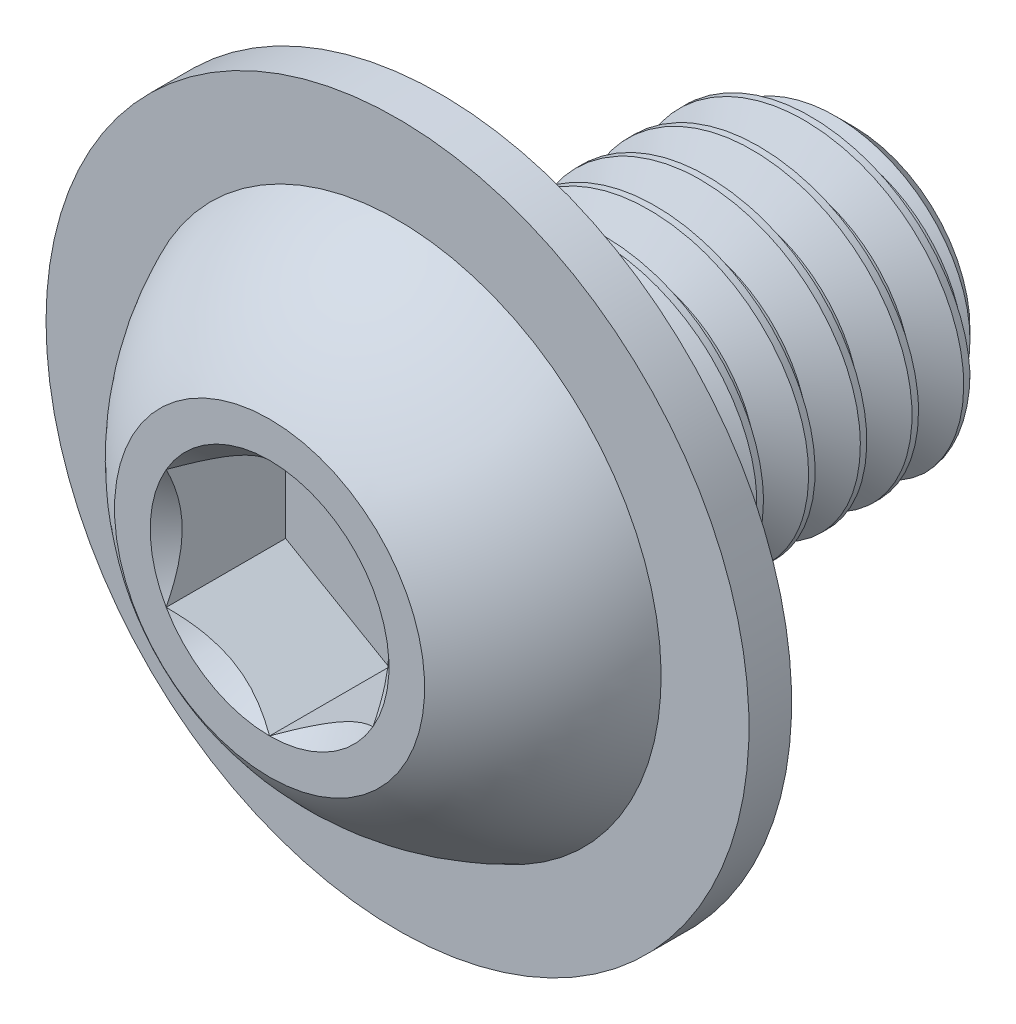
SolidWorks part; units mm, degrees
ref_plane "Front" through (0, 0, 0) normal (0, 0, 1) x (1, 0, 0)
ref_plane "Top" through (0, 0, 0) normal (0, 1, 0) x (1, 0, 0)
ref_plane "Right" through (0, 0, 0) normal (1, 0, 0) x (0, 0, -1)
sketch "Sketch1" plane through (0, 0, 0) normal (1, 0, 0) x (0, 0, -1)
  line L2 (3.3, 3) -> (11.3, 3)
  line L3 (11.3, 3) -> (11.3, 0)
  line L4 (11.3, 0) -> (3.3, 0)
  line L6 (2.475, 5.1) -> (3.3, 5.1) construction
  line L7 (11.3, 3) -> (11.3, -3) construction
  line L8 (0, 0) -> (3.3, 0) construction
  line L9 (3.3, 5.1) -> (3.3, -5.1) construction
  line L11 (3.3, 3) -> (3.3, 0)
  line L13 (0, 2) -> (0, -2) construction
  line L14 (0, 2) -> (0, 3) construction
  line L15 (2.475, 5.1) -> (2.475, 6.8) construction
  line L16 (2.475, 6.8) -> (3.3, 6.8) construction
  line L17 (3.3, 6.8) -> (3.3, 5.1) construction
  line L18 (3.3, 6.8) -> (3.3, -6.8) construction
  arc A3 (0, 3) -> (2.475, 5.1) centre (4.6739, 0) cw construction
  dimension "D1" = 0.825
revolve "Revolve1" add sketch "Sketch1" angle 360 mid plane about L4
sketch "Sketch3" plane through (0, 0, -11.3) normal (0, 0, -1) x (-1, 0, 0)
  circle A0 centre (0, 0) radius 3
curve "Helix/Spiral1" pitch 1 height 9 turns 9
sketch "Sketch2" plane through (0, 0, 0) normal (1, 0, 0) x (0, 0, -1)
  line L0 (11.3, 3) -> (12.175, 3)
  line L1 (12.175, 3) -> (11.8, 2.3505)
  line L2 (11.8, 2.3505) -> (11.675, 2.3505)
  line L3 (11.675, 2.3505) -> (11.3, 3)
  line L4 (11.4875, 2.6752) -> (11.9875, 2.6752) construction
  dimension "D1" = 60
  dimension "D2" = 0.125
  dimension "D3" = 0.5
chamfer "Chamfer1" distance 0.75 angle 45 1 edges at (0, 3, -11.3)
sweep "Cut-Sweep1" cut profiles "Sketch2" path "Helix/Spiral1" align with end faces yes
sketch "Sketch7" plane through (0, 0, 0) normal (1, 0, 0) x (0, 0, -1)
  line L6 (2.475, 5.1) -> (3.3, 5.1) construction
  line L8 (0, 0) -> (3.3, 0) construction
  line L11 (3.3, 5.1) -> (3.3, -5.1) construction
  line L12 (2.475, 5.1) -> (3.3, 5.1)
  line L13 (0, 0) -> (3.3, 0)
  line L14 (0, 2) -> (0, -2) construction
  line L15 (3.3, 5.1) -> (3.3, 0)
  line L16 (0, 3) -> (0, 0)
  arc A2 (2.475, 5.1) -> (0, 3) centre (4.6739, 0) ccw construction
  arc A3 (2.475, 5.1) -> (0, 3) centre (4.6739, 0) ccw
revolve "Revolve2" add sketch "Sketch7" angle 360 mid plane about L13
sketch "Sketch11" plane through (0, 0, -3.3) normal (0, 0, -1) x (-1, 0, 0)
  circle A0 centre (0, 0) radius 6.8
extrude "Boss-Extrude3" add sketch "Sketch11" against normal up to vertex (0.825 mm away) up to point (0, 5.1, -2.475)
sketch "Sketch5" plane through (0, 0, 0) normal (0, 0, 1) x (1, 0, 0)
  line L1 (2, -1.1547) -> (2, 1.1547)
  line L2 (2, 1.1547) -> (0, 2.3094)
  line L3 (0, 2.3094) -> (-2, 1.1547)
  line L4 (-2, 1.1547) -> (-2, -1.1547)
  line L5 (-2, -1.1547) -> (0, -2.3094)
  line L6 (0, -2.3094) -> (2, -1.1547)
  circle A0 centre (0, 0) radius 2 construction
extrude "Cut-Extrude2" cut sketch "Sketch5" against normal blind 2.31
sketch "Sketch6" plane through (0, 0, 0) normal (0, 0, 1) x (1, 0, 0)
  circle A0 centre (0, 0) radius 2.3094
extrude "Cut-Extrude3" cut sketch "Sketch6" against normal blind 2.31 draft 45
sketch "Sketch9" [suppressed] plane through (0, 0, -5.0546) normal (0, 0, 1) x (1, 0, 0)
  circle A2 centre (0, 0) radius 4.7625
extrude "Boss-Extrude2" [suppressed] add sketch "Sketch9" against normal offset from surface (6.35 mm away) 31.75
sketch "Sketch10" plane through (0, 0, 0) normal (1, 0, 0) x (0, 0, -1)
  line L0 (11.3, 3) -> (11.3, -3) construction
  point P0 (9.8, -3)
  dimension "D1" = 1.5
equation "\"D3@Helix/Spiral1\" = \"Lg@Sketch1\" + \"D4@Helix/Spiral1\""
equation "\"D2@Sketch2\" = \"D4@Helix/Spiral1\" * .125"
equation "\"D3@Sketch2\" = \"D4@Helix/Spiral1\" * .5"
equation "\"D1@Chamfer1\" = \"D4@Helix/Spiral1\" * .75"
equation "\"D1@Cut-Extrude2\" = \"Head Ht@Sketch1\" * .7"
equation "\"D1@Sketch1\" = \"Head Ht@Sketch1\" * .25"
equation "\"D1@Sketch10\" = \"D4@Helix/Spiral1\" * 1.5"
equation "\"D1@Cut-Extrude3\" = \"D1@Cut-Extrude2\""
